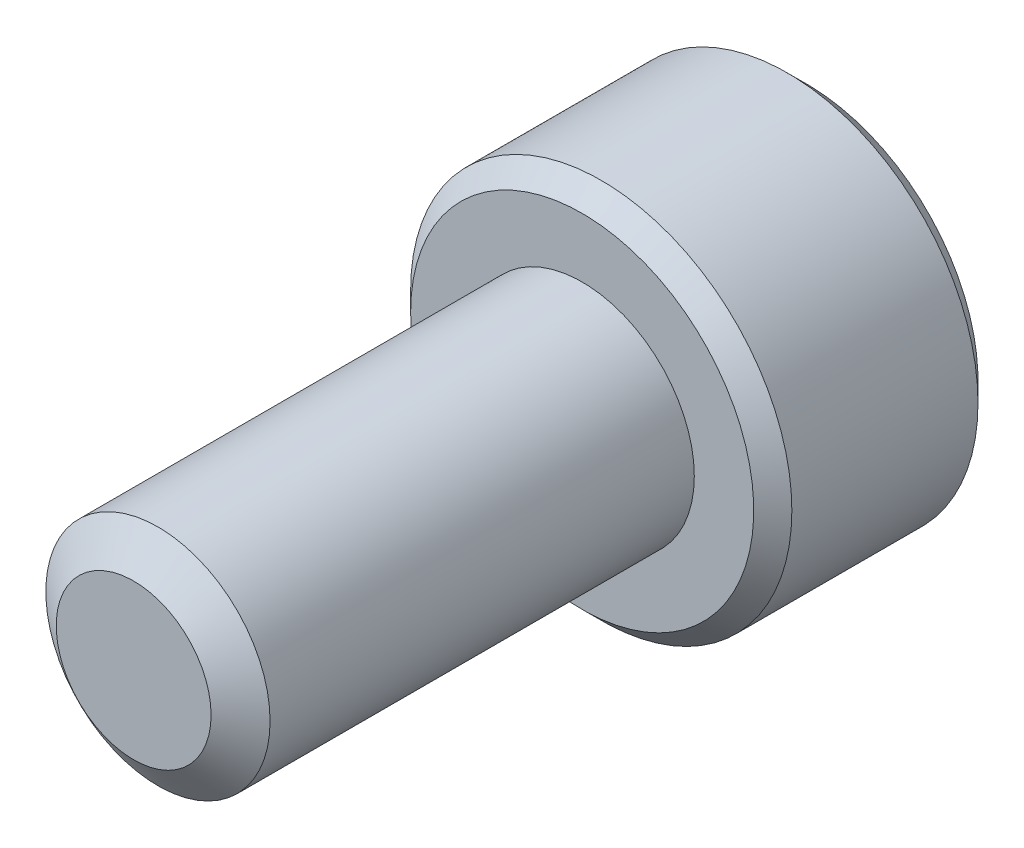
SolidWorks part; units mm, degrees
other "DetailItem1"
material "AISI 304"
ref_plane "Front Plane" through (0, 0, 0) normal (0, 0, 1) x (1, 0, 0)
ref_plane "Top Plane" through (0, 0, 0) normal (0, 1, 0) x (1, 0, 0)
ref_plane "Right Plane" through (0, 0, 0) normal (1, 0, 0) x (0, 0, -1)
sketch "Sketch1" plane through (0, 0, 0) normal (0, 0, 1) x (1, 0, 0)
  circle A0 centre (0, 0) radius 2.5
  dimension "OD" = 5
extrude "Extrude1" add sketch "Sketch1" against normal blind 10
sketch "Sketch2" plane through (0, 0, 0) normal (0, 0, 1) x (1, 0, 0)
  circle A0 centre (0, 0) radius 2.5 construction
  circle A1 centre (0, 0) radius 2.5
curve "Helix/Spiral1" pitch 0.8 height 10.8 turns 13.5 parameters "pitch"=0.8
sketch "Sketch3" plane through (0, 0, 0) normal (1, 0, 0) x (0, 0, -1)
  line L0 (-0.7, 2.5) -> (-0.4, 1.9804)
  line L1 (-0.4, 1.9804) -> (-0.3, 1.9804)
  line L2 (-0.3, 1.9804) -> (0, 2.5)
  line L3 (-0.7, 2.5) -> (0, 2.5)
  line L4 (-0.35, 2.5) -> (-0.35, 1.9804) construction
  line L5 (-0.55, 2.2402) -> (-0.15, 2.2402) construction
  line L6 (0, 2.5) -> (0, -2.5) construction
  dimension "D1" = 0.1
  dimension "D2" = 0.4
  dimension "D3" = 60
sweep "Cut-Sweep1" [suppressed] cut profiles "Sketch3" path "Helix/Spiral1"
sketch "Sketch4" plane through (0, 0, 0) normal (1, 0, 0) x (0, 0, -1)
  line L0 (0.5417, 2.5) -> (0, 1.7264)
  line L1 (0, 1.7264) -> (0, 2.5)
  line L2 (0.5417, 2.5) -> (0, 2.5)
  line L3 (-0.7, 2.5) -> (0, 2.5) construction
  line L4 (0, 0) -> (7.0209, 0) construction
  dimension "D1" = 55
  dimension "D2" = 0.254
revolve "Cut-Revolve1" cut sketch "Sketch4" angle 360 about L4
sketch "Sketch6" plane through (0, 0, -10) normal (0, 0, -1) x (-1, 0, 0)
  circle A0 centre (0, 0) radius 4.25
  dimension "head dia" = 8.5
extrude "Extrude2" add sketch "Sketch6" along normal blind 5
sketch "Sketch7" plane through (0, 0, -15) normal (0, 0, -1) x (-1, 0, 0)
  line L1 (0, 2.3094) -> (-2, 1.1547)
  line L2 (-2, 1.1547) -> (-2, -1.1547)
  line L3 (-2, -1.1547) -> (0, -2.3094)
  line L4 (0, -2.3094) -> (2, -1.1547)
  line L5 (2, -1.1547) -> (2, 1.1547)
  line L6 (2, 1.1547) -> (0, 2.3094)
  circle A0 centre (0, 0) radius 2 construction
  dimension "hex dia" = 4
extrude "Cut-Extrude1" cut sketch "Sketch7" against normal blind 3
sketch "Sketch8" plane through (0, 0, -15) normal (0, 0, -1) x (-1, 0, 0)
  circle A0 centre (0, 0) radius 2.3094
extrude "Cut-Extrude2" cut sketch "Sketch8" against normal through all draft 45
chamfer "Chamfer1" distance 0.425 angle 45 2 edges at (-4.25, 0, -15) (-4.25, 0, -10)
sketch "Sketch10" plane through (0, 0, -10) normal (0, 0, 1) x (1, 0, 0)
  circle A1 centre (0, 0) radius 2.5
  circle A2 centre (0, 0) radius 2.5
  dimension "D1" = 0
ref_plane "Plane1" through (0, 0, 0) normal (0, 0, 1) x (1, 0, 0)
extrude "partial thread" [suppressed] add sketch "Sketch10" along normal up to surface (13 mm away) separate body up to plane "Plane1"
chamfer "Chamfer2" [suppressed] distance 0.1 angle 45
combine bodies "Combine1" [suppressed] operation type add bodies to combine 107 108
sketch "Sketch9" plane through (0, 0, 0) normal (1, 0, 0) x (0, 0, -1)
  line L0 (0, 2.5) -> (0, -2.5) construction
  line L1 (2, 2.5) -> (2, -2.5) construction
  dimension "D1" = 2
equation "\"D3@Helix/Spiral1\" = \"screw length@Extrude1\"+\"pitch@Helix/Spiral1\""
equation "\"D1@Sketch3\" = \"pitch@Helix/Spiral1\"*.125"
equation "\"D2@Sketch3\" = \"pitch@Helix/Spiral1\"*.5"
equation "\"D1@Cut-Extrude1\" = \"hex dia@Sketch7\"*.75"
equation "\"D1@Chamfer1\" = \"head dia@Sketch6\"*.05"
equation "\"D1@Sketch9\" = \"pitch@Helix/Spiral1\"*2.5"
equation "\"D1@Chamfer2\"=\"OD@Sketch1\"*.02"
